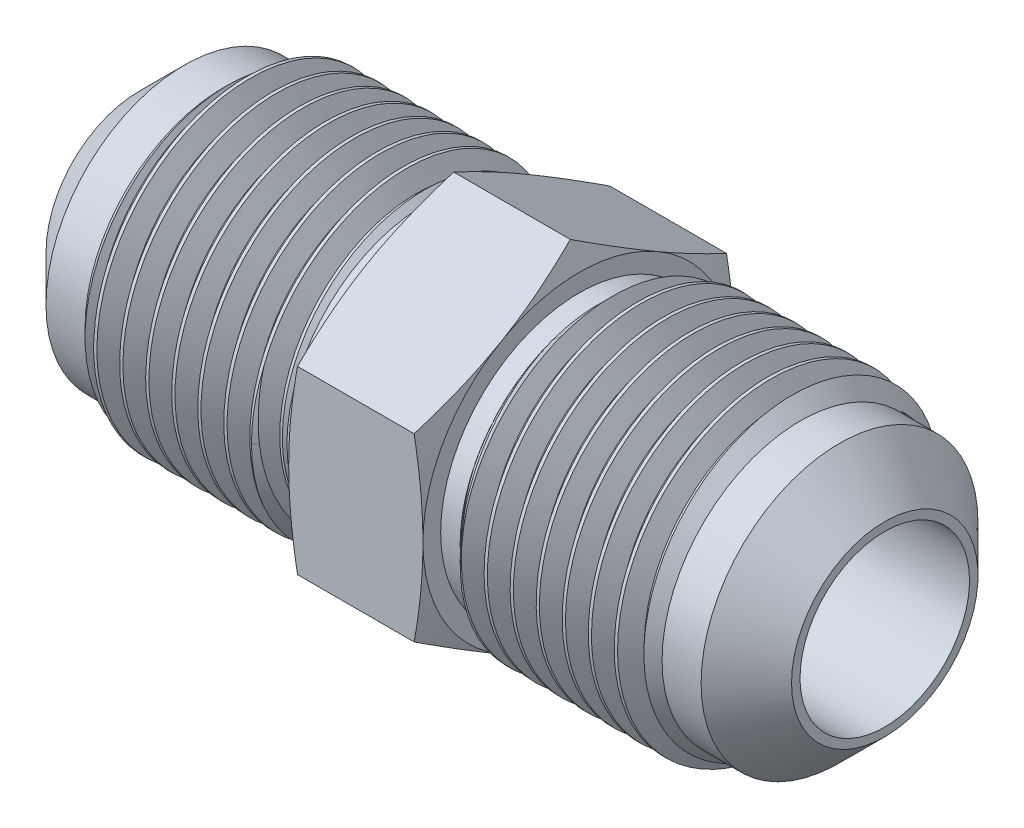
SolidWorks part; units mm, degrees
material "Brass"
ref_plane "Front" through (0, 0, 0) normal (0, 0, 1) x (1, 0, 0)
ref_plane "Top" through (0, 0, 0) normal (0, 1, 0) x (1, 0, 0)
ref_plane "Right" through (0, 0, 0) normal (1, 0, 0) x (0, 0, -1)
sketch "Sketch6" plane through (0, 0, 0) normal (0, 0, 1) x (1, 0, 0)
  line L1 (22.733, 9.525) -> (22.733, -9.525) construction
  line L2 (-22.733, 0) -> (22.733, 0)
  line L4 (-22.733, 0) -> (-22.733, 9.525)
  line L5 (-22.733, 9.525) -> (22.733, 9.525)
  line L6 (22.733, 0) -> (22.733, 9.525)
  point P4 (4.0919, 0)
  point P6 (-4.0919, 0)
  dimension "Straight Dia" = 19.05
  dimension "Length" = 45.466
  dimension "L1" = 18.6411
  dimension "D1" = 18.6411
revolve "Revolve3" add sketch "Sketch6" angle 360 about L2
sketch "Sketch14" plane through (-22.733, 0, 0) normal (-1, 0, 0) x (0, 0, 1)
  circle A0 centre (0, 0) radius 9.525
  circle A2 centre (0, 0) radius 9.525 construction
curve "Helix/Spiral1" pitch 1.5875 height 47.0535 radius 9.525 centre (-22.733, 0, 0) axis (1, 0, 0) start towards (0, 1, 0) parameters "Pitch"=1.5875
sketch "Sketch15" plane through (0, 0, 0) normal (0, 0, 1) x (1, 0, 0)
  line L0 (-24.1221, 9.525) -> (-22.733, 9.525)
  line L1 (-22.733, 9.525) -> (-23.3283, 8.4939)
  line L2 (-23.3283, 8.4939) -> (-23.5267, 8.4939)
  line L3 (-23.5267, 8.4939) -> (-24.1221, 9.525)
  line L4 (-23.4275, 8.4939) -> (-23.4275, 9.525) construction
  line L5 (-23.8244, 9.0094) -> (-23.0307, 9.0094) construction
  dimension "D1" = 60
  dimension "D2" = 0.1984
  dimension "D3" = 0.7937
sweep "Cut-Sweep1" cut profiles "Sketch15" path "Helix/Spiral1" align with end faces yes
ref_plane "Plane1" through (-4.0919, 0, 0) normal (1, 0, 0) x (0, 0, -1)
sketch "Sketch12" plane through (-4.0919, 0, 0) normal (1, 0, 0) x (0, 0, -1)
  line L1 (0, 10.9985) -> (-9.525, 5.4993)
  line L2 (-9.525, 5.4993) -> (-9.525, -5.4993)
  line L3 (-9.525, -5.4993) -> (0, -10.9985)
  line L4 (0, -10.9985) -> (9.525, -5.4993)
  line L5 (9.525, -5.4993) -> (9.525, 5.4993)
  line L6 (9.525, 5.4993) -> (0, 10.9985)
  circle A0 centre (0, 0) radius 9.525 construction
  dimension "Hex" = 19.05
extrude "Extrude1" add sketch "Sketch12" along normal up to vertex (8.1839 mm away) separate body up to point (4.0919, 0, 0)
sketch "Sketch10" plane through (0, 0, 0) normal (0, 0, 1) x (1, 0, 0)
  line L0 (-22.733, 9.525) -> (-22.733, 5.6858)
  line L1 (-4.0919, 9.525) -> (4.0919, 9.525)
  line L2 (-22.733, 5.6858) -> (-19.9757, 8.4431)
  line L3 (-19.9757, 8.4431) -> (-17.5945, 8.4431)
  line L4 (-17.5945, 8.4431) -> (-16.5125, 9.525)
  line L5 (-16.5125, 9.525) -> (-22.733, 9.525)
  line L6 (-6.3645, 9.525) -> (-4.0919, 9.525)
  line L8 (-4.0919, 9.525) -> (-4.0919, 8.4431) construction
  line L9 (-4.0919, 8.4431) -> (-5.2826, 8.4431)
  line L10 (4.0919, 8.4431) -> (-4.0919, 8.4431)
  line L11 (-5.2826, 8.4431) -> (-6.3645, 9.525)
  line L13 (-22.733, 5.6858) -> (-22.733, -5.6858) construction
  line L14 (-22.733, 0) -> (0, 0) construction
  line L15 (-22.733, 0) -> (22.733, 0) construction
  line L16 (-4.0919, 10.9985) -> (-4.0919, 5.4993) construction
  line L17 (-22.733, 9.525) -> (22.733, 9.525) construction
  line L18 (0, 0) -> (0, 10.9985) construction
  line L19 (4.0919, 10.9985) -> (-4.0919, 10.9985) construction
  line L20 (5.2826, 8.4431) -> (6.3645, 9.525)
  line L21 (4.0919, 8.4431) -> (5.2826, 8.4431)
  line L22 (4.0919, 9.525) -> (4.0919, 8.4431) construction
  line L23 (6.3645, 9.525) -> (4.0919, 9.525)
  line L24 (16.5125, 9.525) -> (22.733, 9.525)
  line L25 (17.5945, 8.4431) -> (16.5125, 9.525)
  line L26 (19.9757, 8.4431) -> (17.5945, 8.4431)
  line L27 (22.733, 5.6858) -> (19.9757, 8.4431)
  line L28 (22.733, 9.525) -> (22.733, 5.6858)
  line L29 (-14.0017, -9.525) -> (-14.0018, 9.525) construction
  line L30 (0, 0) -> (-14.0017, 0) construction
  point P38 (-14.0017, -9.525)
  dimension "D1" = 45
  dimension "D2" = 1.1906
  dimension "D3" = 45
  dimension "D4" = 45
  dimension "D5" = 11.3716
  dimension "D6" = 2.3813
  dimension "D7" = 0.0508
  dimension "D8" = 8.7312
revolve "Cut-Revolve6" cut sketch "Sketch10" angle 360 about L2
combine bodies "Combine2" operation type add bodies to combine 159 163
sketch "Sketch7" plane through (0, 0, 0) normal (0, 0, 1) x (1, 0, 0)
  line L0 (-22.733, 0) -> (-22.733, 5.1689)
  line L2 (-22.733, 5.1689) -> (22.733, 5.1689)
  line L4 (22.733, 0) -> (22.733, 9.525) construction
  line L11 (22.733, 5.1689) -> (22.733, 0)
  line L12 (22.733, 0) -> (-22.733, 0)
  line L13 (-22.733, 5.1689) -> (-22.733, -5.1689) construction
  dimension "ID" = 10.3378
revolve "Cut-Revolve5" cut sketch "Sketch7" angle 360 about L12
sketch "Sketch16" plane through (-4.0919, 0, 0) normal (-1, 0, 0) x (0, 0, 1)
  circle A0 centre (0, 0) radius 9.525 construction
  circle A1 centre (0, 0) radius 9.525
extrude "Cut-Extrude1" cut sketch "Sketch16" against normal through all draft 70 flip side to cut
sketch "Sketch17" plane through (4.0919, 0, 0) normal (1, 0, 0) x (0, 0, -1)
  circle A1 centre (0, 0) radius 9.525
  circle A2 centre (0, 0) radius 9.525
  dimension "D1" = 0
extrude "Cut-Extrude2" cut sketch "Sketch17" against normal through all draft 70 flip side to cut
equation "\"D2@Sketch15\" = \"Pitch@Helix/Spiral1\"*.125"
equation "\"D3@Sketch15\" = \"Pitch@Helix/Spiral1\"*.50"
equation "\"D3@Helix/Spiral1\" = \"Length@Sketch6\"+\"Pitch@Helix/Spiral1\""
equation "\"D2@Sketch10\" = \"Pitch@Helix/Spiral1\"*.750"
equation "\"D5@Sketch10\" = \"ID@Sketch7\"*1.1"
equation "\"D6@Sketch10\" = \"Pitch@Helix/Spiral1\"*1.50"
equation "\"D8@Sketch10\" = \"Pitch@Helix/Spiral1\"*5.50"
equation "\"L1@Sketch6\" = \"Length@Sketch6\"*.41"
equation "\"D1@Sketch6\" = \"L1@Sketch6\""
